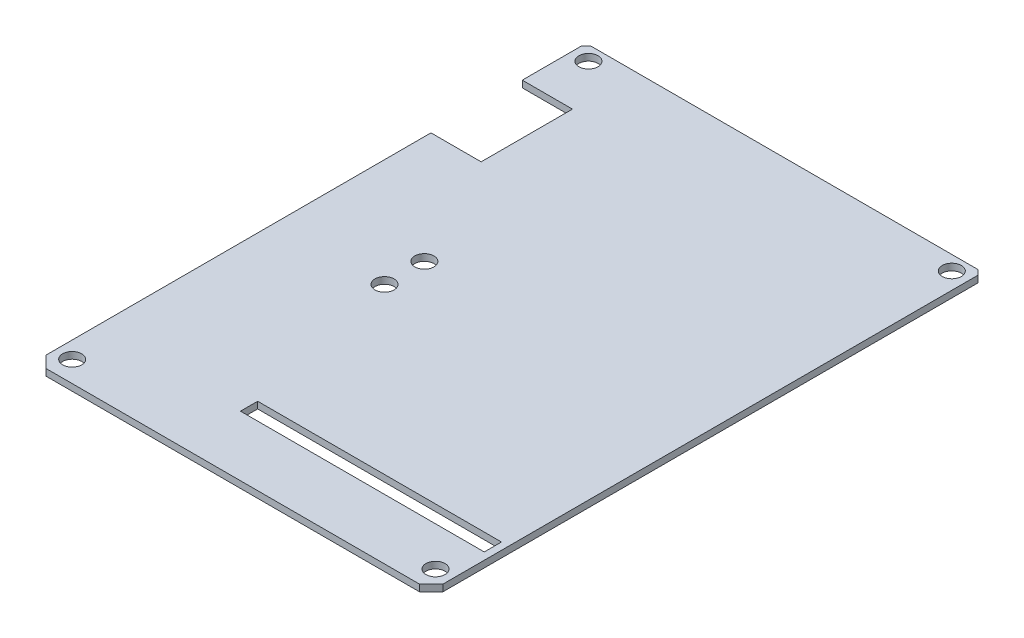
SolidWorks part; units mm, degrees
ref_plane "Front Plane" through (0, 0, 0) normal (0, 0, 1) x (1, 0, 0)
ref_plane "Top Plane" through (0, 0, 0) normal (0, 1, 0) x (1, 0, 0)
ref_plane "Right Plane" through (0, 0, 0) normal (1, 0, 0) x (0, 0, -1)
sketch "Sketch1" plane through (0, 0, 0) normal (0, 1, 0) x (1, 0, 0)
  line L17 (21.25, -27.4901) -> (19.2401, -29.5)
  line L33 (-21.25, 29.5) -> (21.25, 29.5)
  line L34 (-21.25, 29.5) -> (-21.25, -29.5)
  line L35 (-21.25, -29.5) -> (21.25, -29.5)
  line L36 (21.25, 29.5) -> (21.25, -29.5)
  line L37 (-21.25, 29.5) -> (21.25, -29.5) construction
  line L38 (-21.25, -29.5) -> (21.25, 29.5) construction
  line L39 (0, -29.5) -> (0, 29.5) construction
  line L40 (-21.25, -27.4901) -> (-19.2401, -29.5)
  line L41 (21.25, 0) -> (-21.25, 0) construction
  line L42 (21.25, 27.4901) -> (19.2401, 29.5)
  line L43 (-21.25, 27.4901) -> (-19.2401, 29.5)
  line L44 (-20.2401, 28.5) -> (20.2401, 28.5)
  line L45 (-20.2401, -28.5) -> (20.2401, -28.5)
  line L46 (-20.75, -27.9901) -> (-20.75, 27.9901)
  line L47 (20.75, 27.9901) -> (20.75, -27.9901)
  line L56 (-19, -27) -> (19, -27) construction
  circle A13 centre (-9.45, 0.2845) radius 1
  circle A18 centre (-19, -27) radius 1
  circle A19 centre (19, -27) radius 1
  circle A22 centre (-19, 27) radius 1
  circle A23 centre (19, 27) radius 1
  circle A24 centre (-9.45, -3.8845) radius 1
  point P4 (0, 0)
  point P12 (0, 0)
  point P14 (0, 0)
  point P21 (0, -27)
  point P22 (0, 0)
  point P24 (-12.6269, 17.0486)
  dimension "D1" = 42.5
  dimension "D6" = 2.0099
  dimension "D9" = 2
  dimension "D3" = 19
  dimension "D5" = 2.0099
  dimension "D2" = 59
  dimension "D12" = 1
  dimension "D4" = 2
  dimension "D8" = 27
  dimension "D13" = 0.5
  dimension "D14" = 0.5
extrude "Boss-Extrude1" add sketch "Sketch1" along normal blind 0.7 contours L34 L35 L17 L36 L33 A19 A13 region at (0.0253, 0, -0.0048)
sketch "Sketch2" plane through (0, 0.7, 0) normal (0, 1, 0) x (1, 0, 0)
  line L1 (-20, -22.9) -> (20, -22.9)
  line L2 (-20, -22.9) -> (-20, -21.1)
  line L3 (-20, -21.1) -> (20, -21.1)
  line L4 (20, -22.9) -> (20, -21.1)
  line L5 (-20, -22.9) -> (20, -21.1) construction
  line L6 (-20, -21.1) -> (20, -22.9) construction
  line L7 (0, 0) -> (0, -22.9) construction
  line L10 (-5.5029, -21.1) -> (-5.5029, -22.9)
  line L11 (-5.25, -22.6) -> (-5.25, -21.1) construction
  point P4 (0, -22)
  dimension "D1" = 22
  dimension "D2" = 20
  dimension "D3" = 1.8
  dimension "D4" = 0.2529
extrude "Cut-Extrude1" cut sketch "Sketch2" against normal blind 10 contours L3 L10 L1 L4 region at (7.2486, 0.7, 22)
sketch "Sketch5" plane through (0, 0.7, 0) normal (0, 1, 0) x (1, 0, 0)
  line L0 (-20.2401, -28.5) -> (20.2401, -28.5) construction
  line L1 (-19.5401, -28.5) -> (19.5401, -28.5) construction
  line L2 (-19.5401, -28.5) -> (-19.5401, -29.2) construction
  line L3 (-19.5401, -29.2) -> (19.5401, -29.2)
  line L4 (19.5401, -28.5) -> (19.5401, -29.2) construction
  line L5 (-19.5401, -28.5) -> (19.5401, -29.2) construction
  line L6 (-19.5401, -29.2) -> (19.5401, -28.5) construction
  line L7 (0, -28.5) -> (0, -32.1934) construction
  line L9 (-19.5401, -29.2) -> (-20.2401, -28.5)
  line L10 (19.5401, -29.2) -> (20.2401, -28.5)
  line L11 (-20.2401, -28.5) -> (20.2401, -28.5)
  line L12 (-20.75, -27.9901) -> (-20.2401, -28.5) construction
  point P4 (0, -28.85)
  point P11 (18.5758, -28.5)
  point P16 (-20.5591, -28.5)
  point P19 (0, 0)
  dimension "D1" = 0.7
extrude "Boss-Extrude2" add sketch "Sketch5" against normal up to surface (0.7 mm away) up to face at (19, 0, -26)
sketch "Sketch6" plane through (0, 0.7, 0) normal (0, 1, 0) x (1, 0, 0)
  line L0 (-20.75, -27.9901) -> (-20.75, 27.9901) construction
  line L1 (-20.75, 21.8236) -> (-15.5, 21.8236)
  line L2 (-20.75, 21.8236) -> (-20.75, 12.2736)
  line L3 (-20.75, 12.2736) -> (-15.5, 12.2736)
  line L4 (-15.5, 21.8236) -> (-15.5, 12.2736)
  line L5 (-20.75, 21.8236) -> (-15.5, 12.2736) construction
  line L6 (-20.75, 12.2736) -> (-15.5, 21.8236) construction
  line L7 (-12.75, 17.0486) -> (-25.5525, 17.0486) construction
  line L8 (-12.75, 21.4236) -> (-12.75, 12.6736) construction
  point P4 (-18.125, 17.0486)
  point P11 (0, 0)
  dimension "D1" = 9.55
  dimension "D2" = 5.25
extrude "Cut-Extrude2" cut sketch "Sketch6" against normal blind 6
